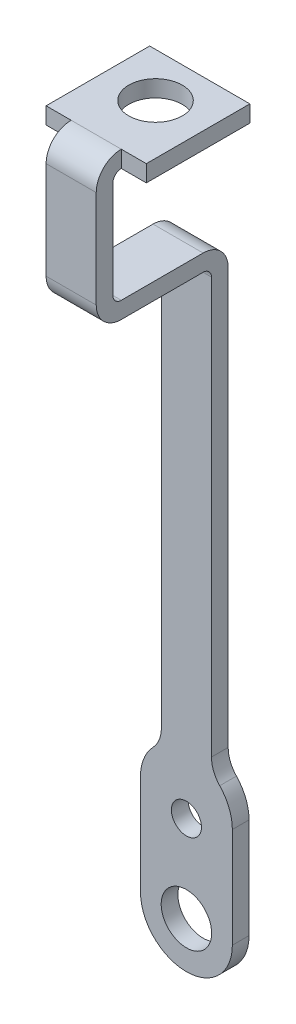
SolidWorks part; units mm, degrees
ref_plane "Front" through (0, 0, 0) normal (0, 0, 1) x (1, 0, 0)
ref_plane "Top" through (0, 0, 0) normal (0, 1, 0) x (1, 0, 0)
ref_plane "Right" through (0, 0, 0) normal (1, 0, 0) x (0, 0, -1)
sketch "草图1" plane through (0, 0, 0) normal (0, 0, 1) x (1, 0, 0)
  line L0 (-1.7, -34.5138) -> (1.6, -34.5138) construction
  line L3 (-1.5, -12.634) -> (-1.5, -39.8461)
  line L4 (1.6, -45.6726) -> (1.6, -34.5138) construction
  line L6 (-1.5, -34.7138) -> (1.4, -34.7138) construction
  line L7 (-1.5, -12.634) -> (0, -12.634)
  line L8 (-1.5, -34.7138) -> (-1.5, -45.8461) construction
  line L9 (1.4, -45.784) -> (1.4, -34.7138) construction
  line L10 (0, -50.901) -> (0, -49.661)
  line L11 (0, -46.641) -> (0, -43.858)
  line L12 (-2.15, -13.884) -> (-1.7, -13.884) construction
  line L13 (-2.95, -82.6664) -> (-2.95, -35.584) construction
  line L14 (-2.95, -48.151) -> (-2.95, -42.151) construction
  line L15 (-2.75, -48.151) -> (-2.75, -42.151)
  line L16 (-1.7, -34.5138) -> (-1.7, -45.7401) construction
  line L17 (0, -42.058) -> (0, -12.634)
  arc A0 (-1.5, -39.8461) -> (-2.75, -42.151) centre (0, -42.151) ccw
  arc A1 (-2.75, -48.151) -> (0, -50.901) centre (0, -48.151) ccw
  arc A2 (-2.95, -48.151) -> (1.6, -45.6726) centre (0, -48.151) ccw construction
  arc A3 (0, -46.641) -> (0, -49.661) centre (0, -48.151) ccw
  arc A5 (-1.5, -45.8461) -> (1.4, -45.784) centre (0, -48.151) ccw construction
  arc A7 (-2, -40.2635) -> (-2.75, -42.151) centre (0, -42.151) ccw construction
  arc A8 (-1.7, -45.7401) -> (1.6, -45.6726) centre (0, -48.151) ccw construction
  arc A9 (0, -42.058) -> (0, -43.858) centre (0, -42.958) ccw
  arc A10 (-2.1455, -40.1263) -> (-2.95, -42.151) centre (0, -42.151) ccw construction
  point P29 (0, 0)
  dimension "D3" = 38.267
  dimension "D2" = 1.25
  dimension "D4" = 1.5
  dimension "D1" = 0.2
extrude "凸台-拉伸1" add sketch "草图1" along normal blind 1
ref_plane "基准面2" through (0, 0, 0) normal (1, 0, 0) x (0, 0, -1)
sketch "草图5" plane through (0, 0, 0) normal (1, 0, 0) x (0, 0, -1)
  line L0 (0, -12.634) -> (-6.9, -12.634)
  line L1 (0, -42.058) -> (0, -12.634) construction
  line L2 (-1, -12.634) -> (0, -12.634) construction
  line L3 (-6.9, -12.634) -> (-6.9, -5.8)
  line L4 (-6.9, -5.8) -> (-0.2, -5.8)
  line L5 (-0.2, -5.8) -> (-0.2, -4.8)
  line L7 (0, -13.634) -> (-7.9, -13.634)
  line L8 (-7.9, -13.634) -> (-7.9, -4.8)
  line L9 (-7.9, -4.8) -> (-0.2, -4.8)
  line L10 (0, -13.634) -> (0, -12.634)
  line L11 (0, -46.641) -> (0, -43.858) construction
  line L13 (-5, -5.8) -> (-0.7, -5.8) construction
  dimension "D1" = 90
  dimension "D3" = 7.9
  dimension "D4" = 0.2
  dimension "D2" = 1
extrude "凸台-拉伸2" add sketch "草图5" against normal up to surface (1.5 mm away) up to face at (-1.5, -26.2401, 0.5)
sketch "草图6" plane through (0, -4.8, 0) normal (0, 1, 0) x (1, 0, 0)
  line L0 (0, -0.2) -> (0, -7.9) construction
  line L1 (-1.5, -6.4) -> (-3, -6.4)
  line L2 (-1.5, -6.4) -> (-1.5, -0.2)
  line L3 (-1.5, -0.2) -> (-3, -0.2)
  line L4 (-3, -6.4) -> (-3, -0.2)
  line L5 (-1.5, -7.9) -> (0, -7.9) construction
  dimension "D1" = 3
  dimension "D2" = 1.5
extrude "凸台-拉伸3" add sketch "草图6" against normal up to surface (1 mm away) up to face at (-0.75, -5.8, 3.55)
sketch "草图7" plane through (0, -4.8, 0) normal (0, 1, 0) x (1, 0, 0)
  line L0 (0, -0.2) -> (0, -7.9) construction
  circle A0 centre (0, -2.85) radius 1.6
  circle A2 centre (0, -2.85) radius 1.65 construction
  dimension "D1" = 3.2
extrude "切除-拉伸1" cut sketch "草图7" against normal up to next
fillet "圆角4" radius 1.8 1 edges at (-1.5, -39.8461, 0.5)
mirror "镜向1" about plane through (0, -46.641, 1) normal (-1, 0, 0) of bodies 105 102
fillet "圆角1" radius 0.5 3 edges at (0, -5.8, 6.9) (0, -12.634, 6.9) (0, -13.634, 1)
fillet "圆角2" radius 1.5 3 edges at (0, -4.8, 7.9) (0, -13.634, 7.9) (0, -12.634, 0)
sketch "草图8" plane through (0, 0, 1) normal (0, 0, 1) x (1, 0, 0)
  line L5 (1.5, -39.0185) -> (1.5, -14.134)
  line L6 (1.5, -14.134) -> (-1.5, -14.134)
  line L7 (-1.5, -14.134) -> (-1.5, -39.0185)
  line L8 (-2.75, -42.151) -> (-2.75, -48.151)
  line L9 (2.75, -48.151) -> (2.75, -42.151)
  line L10 (1.5, -39.0185) -> (1.5, -14.134)
  line L11 (1.5, -14.134) -> (-1.5, -14.134)
  line L12 (-1.5, -14.134) -> (-1.5, -39.0185)
  line L13 (-2.75, -42.151) -> (-2.75, -48.151)
  line L14 (2.75, -48.151) -> (2.75, -42.151)
  circle A0 centre (0, -42.958) radius 0.9 construction
  circle A1 centre (0, -48.151) radius 1.51 construction
  circle A2 centre (0, -42.958) radius 0.9
  circle A3 centre (0, -48.151) radius 1.51
  arc A5 (-1.9945, -40.2577) -> (-1.5, -39.0185) centre (-3.3, -39.0185) ccw
  arc A6 (-1.9945, -40.2577) -> (-2.75, -42.151) centre (0, -42.151) ccw
  arc A7 (-2.75, -48.151) -> (2.75, -48.151) centre (0, -48.151) ccw
  arc A8 (2.75, -42.151) -> (1.9945, -40.2577) centre (0, -42.151) ccw
  arc A9 (1.5, -39.0185) -> (1.9945, -40.2577) centre (3.3, -39.0185) ccw
  arc A10 (-1.9945, -40.2577) -> (-1.5, -39.0185) centre (-3.3, -39.0185) ccw
  arc A11 (-1.9945, -40.2577) -> (-2.75, -42.151) centre (0, -42.151) ccw
  arc A12 (-2.75, -48.151) -> (2.75, -48.151) centre (0, -48.151) ccw
  arc A13 (2.75, -42.151) -> (1.9945, -40.2577) centre (0, -42.151) ccw
  arc A14 (1.5, -39.0185) -> (1.9945, -40.2577) centre (3.3, -39.0185) ccw
  dimension "D1" = 0
sketch "草图9" plane through (0, 0, 0) normal (0, 0, 1) x (1, 0, 0)
  line L0 (-1.7, -34.5138) -> (1.6, -34.5138) construction
  line L3 (-1.5, -12.634) -> (-1.5, -39.8461)
  line L4 (1.6, -45.6726) -> (1.6, -34.5138) construction
  line L6 (-1.5, -34.7138) -> (1.4, -34.7138) construction
  line L7 (-1.5, -12.634) -> (0, -12.634)
  line L8 (-1.5, -34.7138) -> (-1.5, -45.8461) construction
  line L9 (1.4, -45.784) -> (1.4, -34.7138) construction
  line L10 (0, -50.901) -> (0, -49.661)
  line L11 (0, -46.641) -> (0, -43.858)
  line L14 (-2.95, -48.151) -> (-2.95, -42.151) construction
  line L15 (-2.75, -48.151) -> (-2.75, -42.151)
  line L16 (-1.7, -34.5138) -> (-1.7, -45.7401) construction
  line L17 (0, -42.058) -> (0, -12.634)
  arc A0 (-1.5, -39.8461) -> (-2.75, -42.151) centre (0, -42.151) ccw
  arc A1 (-2.75, -48.151) -> (0, -50.901) centre (0, -48.151) ccw
  arc A2 (-2.95, -48.151) -> (1.6, -45.6726) centre (0, -48.151) ccw construction
  arc A3 (0, -46.641) -> (0, -49.661) centre (0, -48.151) ccw
  arc A5 (-1.5, -45.8461) -> (1.4, -45.784) centre (0, -48.151) ccw construction
  arc A7 (-2, -40.2635) -> (-2.75, -42.151) centre (0, -42.151) ccw construction
  arc A8 (-1.7, -45.7401) -> (1.6, -45.6726) centre (0, -48.151) ccw construction
  arc A9 (0, -42.058) -> (0, -43.858) centre (0, -42.958) ccw
  arc A10 (-2.1455, -40.1263) -> (-2.95, -42.151) centre (0, -42.151) ccw construction
  point P29 (0, 0)
  dimension "D3" = 38.267
  dimension "D4" = 1.5
  dimension "D1" = 0.2
